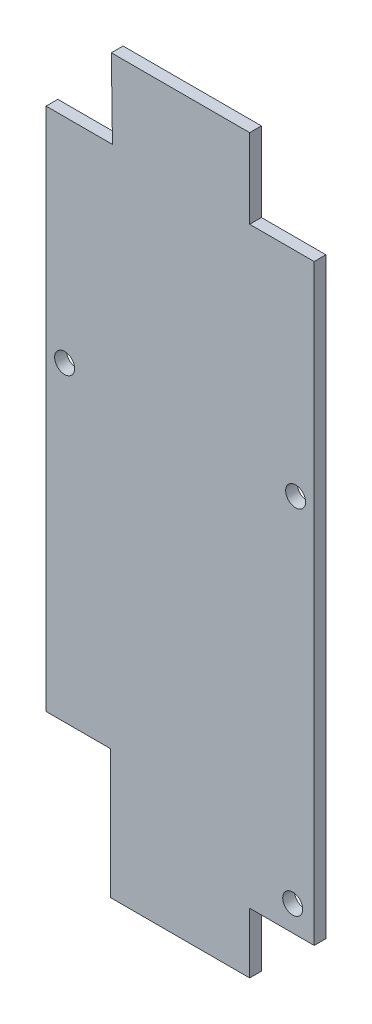
SolidWorks part; units mm, degrees
ref_plane "Front Plane" through (0, 0, 0) normal (0, 0, 1) x (1, 0, 0)
ref_plane "Top Plane" through (0, 0, 0) normal (0, 1, 0) x (1, 0, 0)
ref_plane "Right Plane" through (0, 0, 0) normal (1, 0, 0) x (0, 0, -1)
sketch "Sketch1" plane through (0, 0, 0) normal (0, 0, 1) x (1, 0, 0)
  line L61 (-30.8483, -49.6887) -> (-30.8483, -98.317)
  line L62 (-30.8483, -98.317) -> (-22.1171, -98.317)
  line L63 (-22.1171, -98.317) -> (-22.1171, -115.7795)
  line L64 (-22.1171, -115.7795) -> (-3.283, -115.7795)
  line L65 (-3.283, -115.7795) -> (-3.283, -98.317)
  line L66 (-3.283, -98.317) -> (5.4483, -98.317)
  line L67 (5.4483, -98.317) -> (5.4483, -49.6887)
  line L71 (5.4483, -49.6887) -> (5.4483, -27.4129)
  line L72 (5.4483, -27.4129) -> (-3.283, -27.4129)
  line L73 (-3.283, -27.4129) -> (-3.283, -16.6687)
  line L74 (-3.283, -16.6687) -> (-22.0149, -16.6687)
  line L75 (-22.0149, -16.6687) -> (-21.8622, -27.3367)
  line L76 (-21.8622, -27.3367) -> (-30.8483, -27.3367)
  line L77 (-30.8483, -27.3367) -> (-30.8483, -49.6887)
extrude "Boss-Extrude1" add sketch "Sketch1" along normal blind 1.5875
sketch "Sketch2" plane through (0, 0, 1.5875) normal (0, 0, 1) x (1, 0, 0)
  line L0 (5.4483, -98.317) -> (5.4483, -27.4129) construction
  line L1 (-3.283, -98.317) -> (5.4483, -98.317)
  line L2 (-3.283, -98.317) -> (-3.283, -107.6007)
  line L3 (-3.283, -107.6007) -> (5.4483, -107.6007)
  line L4 (5.4483, -98.317) -> (5.4483, -107.6007)
  line L5 (-3.283, -98.317) -> (5.4483, -107.6007) construction
  line L6 (-3.283, -107.6007) -> (5.4483, -98.317) construction
  line L7 (-3.283, -98.317) -> (5.4483, -98.317) construction
  point P4 (1.0827, -102.9589)
extrude "Boss-Extrude2" add sketch "Sketch2" against normal through all
hole_wizard "#2 Clearance Hole1" positions "Sketch4" profile "Sketch3" hole size "#2" standard "ANSI Inch" end condition through all
sketch "Sketch4" plane through (0, 0, 1.5875) normal (0, 0, 1) x (1, 0, 0)
  point P0 (2.54, -104.14)
  point P2 (-28.3369, -56.1975)
  point P4 (2.9369, -56.1975)
sketch "Sketch3" plane through (2.54, -104.14, 1.5875) normal (1, 0, 0) x (0, -1, 0)
  line L0 (0, 0) -> (0, 1.5875)
  line L1 (0, 1.5875) -> (1.3525, 1.5875)
  line L2 (1.3525, 1.5875) -> (1.3525, 0)
  line L5 (1.3525, 0) -> (0, 0)
  line L11 (0, -6.35) -> (0, 107.95) construction
  dimension "Thru Hole Dia." = 2.7051
  dimension "Thru Hole Depth" = 1.5875
